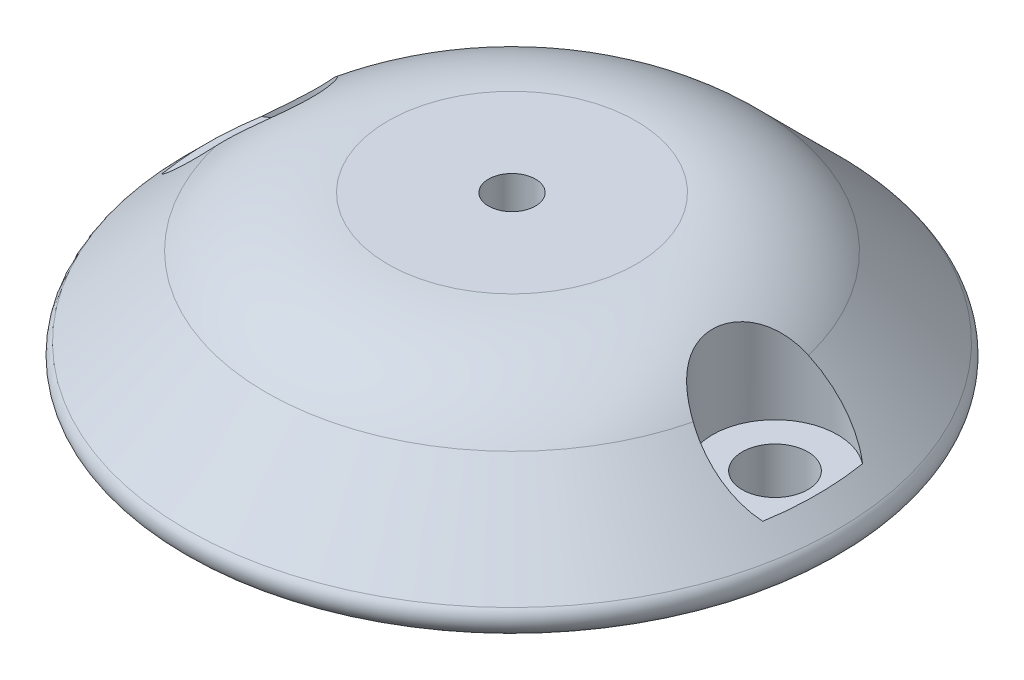
SolidWorks part; units mm, degrees
ref_plane "Front" through (0, 0, 0) normal (0, 0, 1) x (1, 0, 0)
ref_plane "Top" through (0, 0, 0) normal (0, 1, 0) x (1, 0, 0)
ref_plane "Right" through (0, 0, 0) normal (1, 0, 0) x (0, 0, -1)
sketch "Sketch1" plane through (0, 0, 0) normal (0, 1, 0) x (1, 0, 0)
  circle A0 centre (0, 0) radius 22.5
  dimension "D1" = 45
extrude "Boss-Extrude1" add sketch "Sketch1" along normal blind 10 draft 45
sketch "Sketch3" plane through (0, 0, 0) normal (0, -1, 0) x (-1, 0, 0)
  line L1 (10, 14) -> (-10, 14)
  line L2 (10, 14) -> (10, -14)
  line L3 (10, -14) -> (-10, -14)
  line L4 (-10, 14) -> (-10, -14)
  line L5 (10, 14) -> (-10, -14) construction
  line L6 (10, -14) -> (-10, 14) construction
  point P0 (0, 0)
  dimension "D1" = 20
  dimension "D2" = 28
extrude "Cut-Extrude1" cut sketch "Sketch3" against normal blind 5.8
fillet "Fillet1" radius 1 1 edges at (0, 0, 22.5)
fillet "Fillet2" radius 11 1 edges at (0, 10, 12.5)
fillet "Fillet3" radius 2 4 edges at (-10, 2.6477, 14) (10, 2.6477, -14) (10, 2.6477, 14) (-10, 2.6477, -14)
ref_plane "Plane1" through (0, 10, 0) normal (0, 1, 0) x (1, 0, 0)
sketch "Sketch5" plane through (0, 10, 0) normal (0, 1, 0) x (1, 0, 0)
  line L0 (-16.83, 0) -> (16.83, 0) construction
  circle A0 centre (-16.83, 0) radius 4
  circle A1 centre (16.83, 0) radius 4
  point P6 (0, 0)
  dimension "D2" = 8
  dimension "D1" = 33.66
extrude "Cut-Extrude2" cut sketch "Sketch5" against normal blind 7
sketch "Sketch6" plane through (0, 10, 0) normal (0, 1, 0) x (1, 0, 0)
  circle A0 centre (-16.83, 0) radius 2.1
  circle A1 centre (16.83, 0) radius 2.1
  dimension "D1" = 4.2
extrude "Cut-Extrude3" cut sketch "Sketch6" against normal through all
sketch "Sketch7" plane through (0, 10, 0) normal (0, 1, 0) x (1, 0, 0)
  circle A0 centre (0, 0) radius 1.5
  dimension "D1" = 3
extrude "Cut-Extrude4" cut sketch "Sketch7" against normal through all
